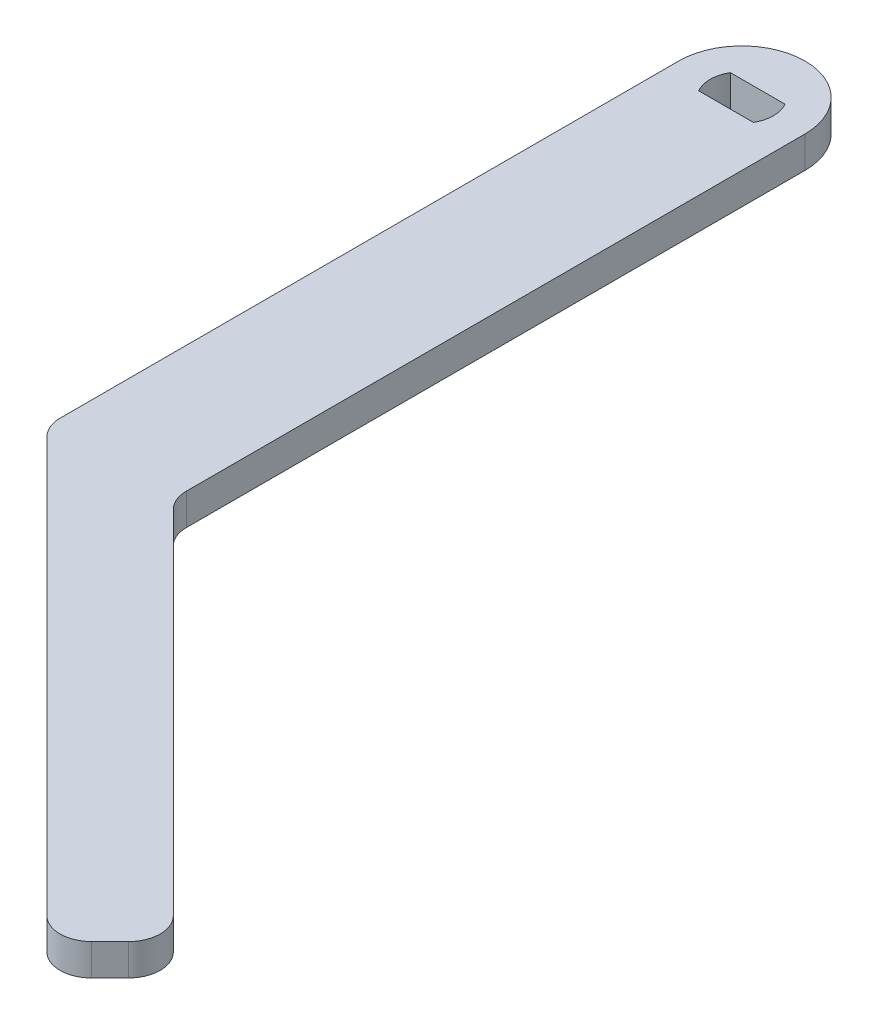
SolidWorks part; units mm, degrees
material "ABS"
ref_plane "Front Plane" through (0, 0, 0) normal (0, 0, 1) x (1, 0, 0)
ref_plane "Top Plane" through (0, 0, 0) normal (0, 1, 0) x (1, 0, 0)
ref_plane "Right Plane" through (0, 0, 0) normal (1, 0, 0) x (0, 0, -1)
sketch "Sketch1" plane through (0, 0, 0) normal (0, 1, 0) x (1, 0, 0)
  circle A0 centre (0, 0) radius 30
  dimension "D1" = 60
extrude "Boss-Extrude1" add sketch "Sketch1" along normal blind 200
sketch "Sketch2" plane through (0, 200, 0) normal (0, 1, 0) x (1, 0, 0)
  circle A0 centre (0, -50) radius 4
  circle A2 centre (0, 0) radius 30 construction
  dimension "D1" = 8
  dimension "D2" = 50
extrude "Boss-Extrude2" add sketch "Sketch2" against normal blind 80 from offset 60 separate body offset against normal yes
sketch "Sketch4" plane through (0, 140, 0) normal (0, 1, 0) x (1, 0, 0)
  line L6 (-2.9328, -47.28) -> (40.9159, 0)
  line L7 (2.9328, -52.72) -> (51.8267, 0)
  line L8 (40.9159, 0) -> (6, 37.6481)
  line L9 (51.8267, 0) -> (11.8657, 43.0881)
  line L10 (6, 37.6481) -> (11.8657, 43.0881)
  circle A0 centre (0, -50) radius 4 construction
  circle A1 centre (0, 0) radius 30 construction
  arc A2 (2.9328, -52.72) -> (-2.9328, -47.28) centre (0, -50) ccw
  dimension "D2" = 6
  dimension "D4" = 8
  dimension "D5" = 8
  dimension "D6" = 8
extrude "Boss-Extrude3" add sketch "Sketch4" against normal blind 10 from offset 10 offset against normal yes
sketch "Sketch5" plane through (0, 60, 0) normal (0, -1, 0) x (1, 0, 0)
  line L0 (6, -37.6481) -> (11.8657, -43.0881) construction
  line L1 (40.9159, 0) -> (6, -37.6481) construction
  line L2 (51.8267, 0) -> (11.8657, -43.0881) construction
  line L3 (2.9328, 52.72) -> (51.8267, 0) construction
  line L4 (-2.9328, 47.28) -> (40.9159, 0) construction
  line L5 (6, -37.6481) -> (11.8657, -43.0881)
  line L6 (40.9159, 0) -> (6, -37.6481)
  line L7 (51.8267, 0) -> (11.8657, -43.0881)
  line L8 (2.9328, 52.72) -> (51.8267, 0)
  line L9 (-2.9328, 47.28) -> (40.9159, 0)
  arc A0 (-2.9328, 47.28) -> (2.9328, 52.72) centre (0, 50) ccw construction
  arc A1 (-2.9328, 47.28) -> (2.9328, 52.72) centre (0, 50) ccw
extrude "Boss-Extrude4" add sketch "Sketch5" against normal blind 10 from offset 10 offset against normal yes
sketch "Sketch7" plane through (0, 140, 0) normal (0, 1, 0) x (1, 0, 0)
  circle A0 centre (0, -50) radius 4
extrude "Cut-Extrude1" cut sketch "Sketch7" against normal blind 12 from offset 34 offset against normal yes
sketch "Sketch8" plane through (0, 140, 0) normal (0, 1, 0) x (1, 0, 0)
  circle A0 centre (0, -50) radius 2
  dimension "D1" = 4
extrude "Cut-Extrude2" cut sketch "Sketch8" against normal blind 70
sketch "Sketch9" plane through (0, 140, 0) normal (0, 1, 0) x (1, 0, 0)
  circle A0 centre (0, -50) radius 2
extrude "Boss-Extrude6" add sketch "Sketch9" against normal blind 70 from offset 0.1
sketch "Sketch11" plane through (0, 140.1, 0) normal (0, 1, 0) x (1, 0, 0)
  line L0 (-0.975, -51.7462) -> (-0.975, -48.2538)
  line L1 (0.975, -48.2538) -> (0.975, -51.7462)
  circle A0 centre (0, -50) radius 2 construction
  circle A1 centre (0, -50) radius 2 construction
  arc A2 (-0.975, -48.2538) -> (-0.975, -51.7462) centre (0, -50) ccw
  arc A3 (0.975, -48.2538) -> (0.975, -51.7462) centre (0, -50) cw
  dimension "D3" = 2
  dimension "D4" = 2
  dimension "D1" = 1.95
  dimension "D2" = 0.975
extrude "Cut-Extrude4" cut sketch "Sketch11" against normal blind 35 from offset 30 offset against normal yes
sketch "Sketch12" plane through (0, 140.1, 0) normal (0, 1, 0) x (1, 0, 0)
  line L1 (-0.5, -48.8) -> (0.5, -48.8)
  line L2 (-0.5, -48.8) -> (-0.5, -51.2)
  line L3 (-0.5, -51.2) -> (0.5, -51.2)
  line L4 (0.5, -48.8) -> (0.5, -51.2)
  dimension "D1" = 0.5
  dimension "D2" = 0.5
  dimension "D3" = 1.2
  dimension "D4" = 2.4
extrude "Cut-Extrude5" cut sketch "Sketch12" against normal blind 20
sketch "Sketch14" plane through (0, 200, 0) normal (0, 1, 0) x (1, 0, 0)
  circle A0 centre (0, 0) radius 30
extrude "Cut-Extrude6" cut sketch "Sketch14" against normal blind 200
sketch "Sketch15" plane through (0, 140, 0) normal (0, 1, 0) x (1, 0, 0)
  circle A0 centre (0, -50) radius 2
extrude "Cut-Extrude7" cut sketch "Sketch15" against normal blind 70 and the other way blind 200
sketch "Sketch18" plane through (0, 130, 0) normal (0, 1, 0) x (1, 0, 0)
  line L5 (2.9328, -52.72) -> (51.8267, 0)
  line L6 (51.8267, 0) -> (11.8657, 43.0881)
  line L7 (11.8657, 43.0881) -> (6, 37.6481)
  line L8 (6, 37.6481) -> (40.9159, 0)
  line L9 (40.9159, 0) -> (-2.9328, -47.28)
  line L10 (2.9328, -52.72) -> (51.8267, 0)
  line L11 (51.8267, 0) -> (11.8657, 43.0881)
  line L12 (11.8657, 43.0881) -> (6, 37.6481)
  line L13 (6, 37.6481) -> (40.9159, 0)
  line L14 (40.9159, 0) -> (-2.9328, -47.28)
  arc A1 (2.9328, -52.72) -> (-2.9328, -47.28) centre (0, -50) ccw
  arc A2 (2.9328, -52.72) -> (-2.9328, -47.28) centre (0, -50) ccw
  dimension "D1" = 0
extrude "Cut-Extrude9" cut sketch "Sketch18" against normal blind 5
sketch "Sketch20" plane through (0, 125, 0) normal (0, 1, 0) x (1, 0, 0)
  line L5 (2.9328, -52.72) -> (51.8267, 0)
  line L6 (51.8267, 0) -> (11.8657, 43.0881)
  line L7 (11.8657, 43.0881) -> (6, 37.6481)
  line L8 (6, 37.6481) -> (40.9159, 0)
  line L9 (40.9159, 0) -> (-2.9328, -47.28)
  line L10 (2.9328, -52.72) -> (51.8267, 0)
  line L11 (51.8267, 0) -> (11.8657, 43.0881)
  line L12 (11.8657, 43.0881) -> (6, 37.6481)
  line L13 (6, 37.6481) -> (40.9159, 0)
  line L14 (40.9159, 0) -> (-2.9328, -47.28)
  arc A1 (2.9328, -52.72) -> (-2.9328, -47.28) centre (0, -50) ccw
  arc A2 (2.9328, -52.72) -> (-2.9328, -47.28) centre (0, -50) ccw
  dimension "D1" = 0
extrude "Cut-Extrude10" cut sketch "Sketch20" against normal blind 5
ref_plane "Plane1" through (0, 100, 0) normal (0, 1, 0) x (1, 0, 0)
sketch "Sketch22" plane through (0, 80, 0) normal (0, 1, 0) x (1, 0, 0)
  line L6 (6, 37.6481) -> (40.9159, 0)
  line L7 (40.9159, 0) -> (-2.9328, -47.28)
  line L8 (2.9328, -52.72) -> (51.8267, 0)
  line L9 (51.8267, 0) -> (11.8657, 43.0881)
  line L10 (11.8657, 43.0881) -> (6, 37.6481)
  line L11 (6, 37.6481) -> (40.9159, 0)
  line L12 (40.9159, 0) -> (-2.9328, -47.28)
  line L13 (2.9328, -52.72) -> (51.8267, 0)
  line L14 (51.8267, 0) -> (11.8657, 43.0881)
  line L15 (11.8657, 43.0881) -> (6, 37.6481)
  arc A1 (2.9328, -52.72) -> (-2.9328, -47.28) centre (0, -50) ccw
  arc A2 (2.9328, -52.72) -> (-2.9328, -47.28) centre (0, -50) ccw
  dimension "D1" = 0
extrude "Cut-Extrude11" cut sketch "Sketch22" against normal blind 10
sketch "Sketch24" plane through (0, 60, 0) normal (0, -1, 0) x (1, 0, 0)
  circle A0 centre (0, 50) radius 4 construction
  circle A1 centre (0, 50) radius 4
extrude "Cut-Extrude12" cut sketch "Sketch24" against normal blind 10
sketch "Sketch25" plane through (0, 140, 0) normal (0, 1, 0) x (1, 0, 0)
  circle A0 centre (0, -50) radius 4 construction
  circle A1 centre (0, -50) radius 4
extrude "Cut-Extrude13" cut sketch "Sketch25" against normal blind 10
fillet "Fillet10" radius 2 1 edges at (0, 130, 52)
sketch "Sketch28" plane through (0, 70, 0) normal (0, -1, 0) x (1, 0, 0)
  line L1 (-7.7664, 66.8906) -> (11.2683, 66.8906)
  line L2 (-7.7664, 66.8906) -> (-7.7664, 36.4785)
  line L3 (-7.7664, 36.4785) -> (11.2683, 36.4785)
  line L4 (11.2683, 66.8906) -> (11.2683, 36.4785)
extrude "Cut-Extrude14" cut sketch "Sketch28" against normal blind 30
sketch "Sketch30" plane through (0, 106, 0) normal (0, -1, 0) x (1, 0, 0)
  line L1 (-4, 50) -> (4, 50)
  line L2 (-4, 50) -> (-4, 90)
  line L4 (4, 50) -> (4, 90)
  line L9 (-4, 90) -> (4, 90)
  line L10 (-4, 90) -> (24.2843, 118.2843)
  line L11 (4, 90) -> (28.2843, 114.2843)
  line L12 (24.2843, 118.2843) -> (28.2843, 114.2843)
  circle A0 centre (0, 50) radius 4 construction
  dimension "D1" = 8
  dimension "D2" = 40
  dimension "D3" = 135
  dimension "D4" = 40
extrude "Boss-Extrude7" add sketch "Sketch30" along normal blind 2 from offset 15 contours L12 L10 L9 L11 | L9 L4 L1 L2 region at (13.066, 106, 103.1675) offset against normal yes
sketch "Sketch31" plane through (0, 106, 0) normal (0, -1, 0) x (1, 0, 0)
  line L1 (-11.9647, 54.8867) -> (12.9558, 54.8867)
  line L2 (-11.9647, 54.8867) -> (-11.9647, 44.889)
  line L3 (-11.9647, 44.889) -> (12.9558, 44.889)
  line L4 (12.9558, 54.8867) -> (12.9558, 44.889)
extrude "Cut-Extrude15" cut sketch "Sketch31" against normal blind 6
sketch "Sketch32" plane through (0, 112, 0) normal (0, -1, 0) x (1, 0, 0)
  arc A0 (2, 50) -> (-2, 50) centre (0, 50) ccw construction
  circle A1 centre (0, 50) radius 4 construction
  circle A2 centre (0, 50) radius 2 construction
  circle A3 centre (0, 50) radius 4
  circle A4 centre (0, 50) radius 2
  arc A5 (2, 50) -> (-2, 50) centre (0, 50) ccw
  circle M1 centre (0, 50) radius 4
  circle M2 centre (0, 50) radius 2
extrude "Boss-Extrude8" add sketch "Sketch32" along normal blind 6 from offset 3 separate body contours A4 M1 M2 region at (-3.8869, 112, 50)
sketch "Sketch33" plane through (0, 103, 0) normal (0, -1, 0) x (1, 0, 0)
  line L0 (-2, 50) -> (2, 50) construction
  circle A0 centre (0, 50) radius 2
extrude "Boss-Extrude9" add sketch "Sketch33" against normal blind 2
sketch "Sketch34" plane through (0, 103, 0) normal (0, -1, 0) x (1, 0, 0)
  line L0 (4, 50) -> (4, 90) construction
  line L1 (4, 90) -> (28.2843, 114.2843) construction
  line L2 (24.2843, 118.2843) -> (28.2843, 114.2843) construction
  line L3 (-4, 90) -> (24.2843, 118.2843) construction
  line L4 (-4, 50) -> (-4, 90) construction
  line L5 (4, 50) -> (4, 90)
  line L6 (4, 90) -> (28.2843, 114.2843)
  line L7 (24.2843, 118.2843) -> (28.2843, 114.2843)
  line L8 (-4, 90) -> (24.2843, 118.2843)
  line L9 (-4, 50) -> (-4, 90)
  circle M1 centre (0, 50) radius 4
extrude "Boss-Extrude10" add sketch "Sketch34" against normal blind 2 contours L9 L5 L6 L7 L8 M1 region at (0, 103, 54.7553)
sketch "Sketch35" plane through (0, 121, 0) normal (0, 1, 0) x (1, 0, 0)
  line L0 (-2, -50) -> (2, -50) construction
  circle A0 centre (0, -50) radius 2
extrude "Cut-Extrude16" cut sketch "Sketch35" against normal blind 2
sketch "Sketch36" plane through (0, 119, 0) normal (0, -1, 0) x (1, 0, 0)
  line L0 (24.2843, 118.2843) -> (28.2843, 114.2843) construction
  line L1 (-4, 50) -> (-4, 90) construction
  line L2 (-4, 90) -> (24.2843, 118.2843) construction
  circle A0 centre (0, 71) radius 1.5
  circle A1 centre (12.9706, 101.3137) radius 1.5
  arc A2 (-4, 50) -> (4, 50) centre (0, 50) ccw construction
  point P9 (0, 46)
  dimension "D1" = 3
  dimension "D2" = 3
  dimension "D5" = 4
  dimension "D6" = 4
  dimension "D3" = 20
  dimension "D4" = 25
extrude "Boss-Extrude11" add sketch "Sketch36" along normal blind 14
fillet "Fillet11" radius 2 11 edges at (0, 105, 54) (0, 119, 54) (0, 121, 54) (-4, 120, 90) (-4, 104, 90) (4, 104, 90) (4, 120, 90) (28.2843, 104, 114.2843) (24.2843, 104, 118.2843) (24.2843, 120, 118.2843) (28.2843, 120, 114.2843)
sketch "Sketch37" plane through (0, 105, 0) normal (0, 1, 0) x (1, 0, 0)
  line L1 (-32.8189, -37.5227) -> (61.8772, -37.5227)
  line L2 (-32.8189, -37.5227) -> (-32.8189, -135.9083)
  line L3 (-32.8189, -135.9083) -> (61.8772, -135.9083)
  line L4 (61.8772, -37.5227) -> (61.8772, -135.9083)
extrude "Cut-Extrude17" cut sketch "Sketch37" along normal blind 30
sketch "Sketch38" plane through (0, 105, 0) normal (0, 1, 0) x (1, 0, 0)
  line L0 (-1.7321, -49) -> (1.7321, -49)
  line L1 (1.7321, -51) -> (-1.7321, -51)
  circle A1 centre (0, -50) radius 2
  point P7 (0, 0)
  point P8 (0, 0)
  dimension "D1" = 4
  dimension "D2" = 2
extrude "Cut-Extrude18" cut sketch "Sketch38" against normal blind 30 contours L1 A1 L0 region at (0, 105, 50)
